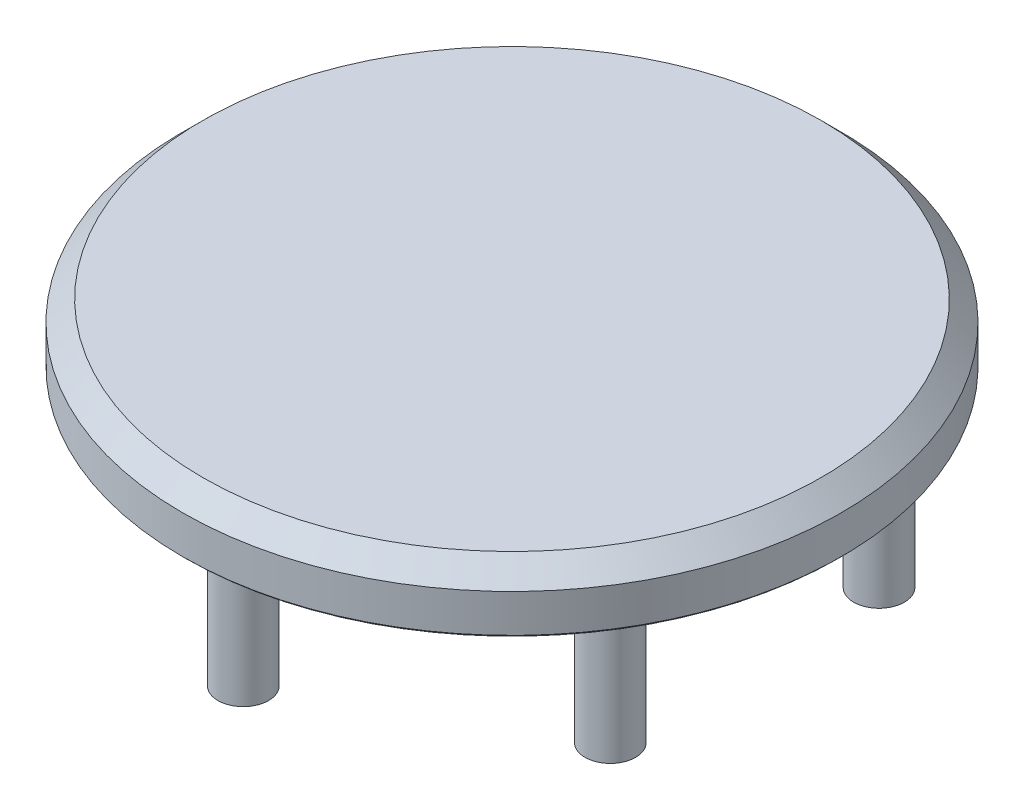
SolidWorks part; units mm, degrees
ref_plane "Front Plane" through (0, 0, 0) normal (0, 0, 1) x (1, 0, 0)
ref_plane "Top Plane" through (0, 0, 0) normal (0, 1, 0) x (1, 0, 0)
ref_plane "Right Plane" through (0, 0, 0) normal (1, 0, 0) x (0, 0, -1)
ref_axis "Axis1" through (0, 0, 0) along (0, 1, 0)
sketch "Sketch3" plane through (0, 0, 0) normal (1, 0, 0) x (0, 0, -1)
  line L0 (0, 0) -> (0, -101510.3777) construction
  line L1 (0, 25) -> (-32.5, 25)
  line L2 (-32.5, 25) -> (-32.5, 31)
  line L3 (-32.5, 31) -> (0, 31)
  line L7 (0, 31) -> (0, 25)
  point P7 (0, 0)
  dimension "D1" = 6
  dimension "D6" = 65
  dimension "D7" = 25
revolve "Revolve1" add sketch "Sketch3" angle 360 about L0
chamfer "Chamfer2" distance 2 angle 45 1 edges at (0, 31, 32.5)
sketch "Sketch4" plane through (0, 25, 0) normal (0, -1, 0) x (1, 0, 0)
  circle A0 centre (0, 26.5) radius 2.5
  dimension "D1" = 5
  dimension "D2" = 26.5
extrude "Boss-Extrude1" add sketch "Sketch4" along normal up to surface (13.8 mm away)
pattern_circular "CirPattern1" count 6 over 360 about axis through (0, 0, 0) along (0, 1, 0) of "Boss-Extrude1"
chamfer "Chamfer3" distance 2 angle 45 6 edges at (0, 25, 24) (-20.7846, 25, 12) (-20.7846, 25, -12) (0, 25, -24) (20.7846, 25, -12) (20.7846, 25, 12)
chamfer "Chamfer4" distance 0.25 angle 45 1 edges at (0, 25, 32.5)
